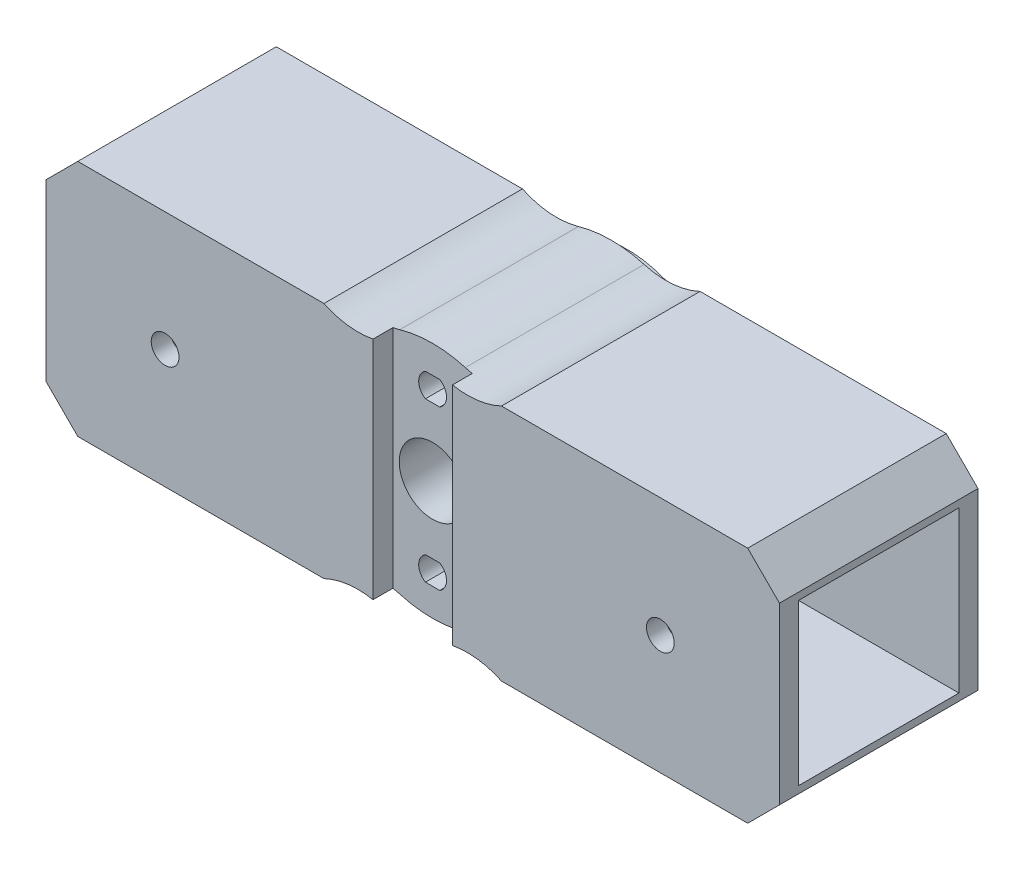
SolidWorks part; units mm, degrees
ref_plane "Alzado" through (0, 0, 0) normal (0, 0, 1) x (1, 0, 0)
ref_plane "Planta" through (0, 0, 0) normal (0, 1, 0) x (1, 0, 0)
ref_plane "Vista lateral" through (0, 0, 0) normal (1, 0, 0) x (0, 0, -1)
sketch "Croquis1" plane through (0, 0, 0) normal (0, 0, 1) x (1, 0, 0)
  circle A0 centre (0, 0) radius 15
  circle A1 centre (0, 0) radius 11.1
  dimension "D1" = 30
  dimension "D2" = 22.2
extrude "Saliente-Extruir1" add sketch "Croquis1" along normal mid plane 25
sketch "Croquis10" plane through (0, 0, 12.5) normal (0, 0, 1) x (1, 0, 0)
  line L0 (11.1803, 0) -> (-11.1803, 0) construction
  line L1 (0, 0) -> (0, 10.6419) construction
  line L2 (-11.1803, -15) -> (-11.1803, 15)
  line L3 (-11.1803, 15) -> (-46.1803, 15)
  line L4 (-46.1803, 15) -> (-46.1803, -15)
  line L5 (-46.1803, -15) -> (-11.1803, -15)
  line L6 (46.1803, 15) -> (46.1803, -15)
  line L7 (11.1803, 15) -> (46.1803, 15)
  line L8 (11.1803, -15) -> (11.1803, 15)
  line L9 (46.1803, -15) -> (11.1803, -15)
  line L10 (-11.1803, 0) -> (-46.1803, 0) construction
  circle A1 centre (-31.1803, 0) radius 1.75
  circle A2 centre (31.1803, 0) radius 1.75
  point P5 (0, 0)
  point P13 (-11.1803, 0)
  point P19 (0, 0)
  point P21 (-32.1622, 0)
  dimension "D3" = 3.5
  dimension "D1" = 35
  dimension "D2" = 30
  dimension "D4" = 15
extrude "Saliente-Extruir8" add sketch "Croquis10" against normal blind 25
sketch "Croquis11" plane through (0, 0, -12.5) normal (0, 0, 1) x (1, 0, 0)
  line L6 (0, 0) -> (0, 7.4469) construction
  line L7 (16.1803, -10) -> (36.1803, -10)
  line L8 (16.1803, 10) -> (16.1803, -10)
  line L9 (36.1803, 10) -> (16.1803, 10)
  line L10 (36.1803, -10) -> (36.1803, 10)
  dimension "D1" = 20
extrude "Cortar-Extruir1" [suppressed] cut sketch "Croquis11" along normal blind 10
sketch "Croquis12" plane through (0, 0, 12.5) normal (0, 0, 1) x (1, 0, 0)
  line L0 (-46.1803, 15) -> (-26.1803, 15)
  line L1 (-11.1803, 15) -> (-46.1803, 15) construction
  line L2 (-26.1803, 15) -> (-26.1803, -15)
  line L3 (-46.1803, -15) -> (-11.1803, -15) construction
  line L4 (-26.1803, -15) -> (-46.1803, -15)
  line L5 (-46.1803, -15) -> (-46.1803, 15)
  dimension "D1" = 20
extrude "Cortar-Extruir2" [suppressed] cut sketch "Croquis12" against normal blind 10
sketch "Croquis13" plane through (0, 0, 12.5) normal (0, 0, 1) x (1, 0, 0)
  circle A0 centre (0, 0) radius 11.1
  circle A1 centre (0, 0) radius 4.2
  dimension "D1" = 22.2
  dimension "D2" = 8.4
extrude "Saliente-Extruir9" add sketch "Croquis13" against normal blind 12.8
sketch "Croquis14" plane through (0, 0, -12.5) normal (0, 0, -1) x (-1, 0, 0)
  circle A0 centre (0, 0) radius 11.1
  circle A1 centre (0, 0) radius 13
  dimension "D1" = 22.2
  dimension "D2" = 26
extrude "Saliente-Extruir10" add sketch "Croquis14" along normal blind 2
sketch "Croquis15" plane through (0, 0, 12.5) normal (0, 0, 1) x (1, 0, 0)
  line L0 (-5, 0) -> (-5, 15)
  line L1 (-5, 15) -> (5, 15)
  line L2 (5, 15) -> (5, -15)
  line L3 (5, -15) -> (-5, -15)
  line L4 (-5, -15) -> (-5, 0)
  point P3 (0, 15)
  dimension "D1" = 10
  dimension "D2" = 30
extrude "Cortar-Extruir3" cut sketch "Croquis15" against normal blind 2.5
sketch "Croquis16" plane through (0, 0, 10) normal (0, 0, 1) x (1, 0, 0)
  line L0 (0, 15) -> (0, 10) construction
  line L1 (0, 10) -> (0, 0) construction
  line L2 (0, 0) -> (0, -10) construction
  line L3 (0, -10) -> (0, -15) construction
  line L4 (-0.9014, 11.5) -> (0.9014, 11.5)
  line L5 (-0.9014, 8.5) -> (0.9014, 8.5)
  line L6 (0, 0) -> (-3.0161, 0) construction
  line L7 (-0.9014, -8.5) -> (0.9014, -8.5)
  line L8 (-0.9014, -11.5) -> (0.9014, -11.5)
  arc A0 (5, 14.1421) -> (-5, 14.1421) centre (0, 0) ccw construction
  arc A1 (-5, -14.1421) -> (5, -14.1421) centre (0, 0) ccw construction
  arc A2 (-0.9014, 11.5) -> (-0.9014, 8.5) centre (0, 10) ccw
  arc A3 (0.9014, 8.5) -> (0.9014, 11.5) centre (0, 10) ccw
  arc A4 (-0.9014, -11.5) -> (-0.9014, -8.5) centre (0, -10) cw
  arc A5 (0.9014, -8.5) -> (0.9014, -11.5) centre (0, -10) cw
  point P16 (0, 11.5)
  point P19 (0, 8.5)
  dimension "D2" = 3.5
  dimension "D1" = 5
  dimension "D3" = 3
extrude "Cortar-Extruir4" cut sketch "Croquis16" against normal blind 7.5
sketch "Croquis17" plane through (-46.1803, 0, 0) normal (-1, 0, 0) x (0, 0, 1)
  line L1 (10.1, 10.1) -> (-10.1, 10.1)
  line L2 (10.1, 10.1) -> (10.1, -10.1)
  line L3 (10.1, -10.1) -> (-10.1, -10.1)
  line L4 (-10.1, 10.1) -> (-10.1, -10.1)
  line L5 (10.1, 10.1) -> (-10.1, -10.1) construction
  line L6 (10.1, -10.1) -> (-10.1, 10.1) construction
  point P0 (0, 0)
  dimension "D1" = 20.2
  dimension "D2" = 20.2
extrude "Cortar-Extruir5" cut sketch "Croquis17" against normal blind 30
mirror "Simetría1" about plane through (0, 0, 0) normal (1, 0, 0) of "Cortar-Extruir5"
fillet "Redondeo1" radius 10 4 edges at (-11.1803, 10, 0) (11.1803, 10, 0) (-11.1803, -10, 0) (11.1803, -10, 0)
chamfer "Chaflán1" distance 4 angle 45 4 edges at (46.1803, 15, 0) (46.1803, -15, 0) (-46.1803, 15, 0) (-46.1803, -15, 0)
